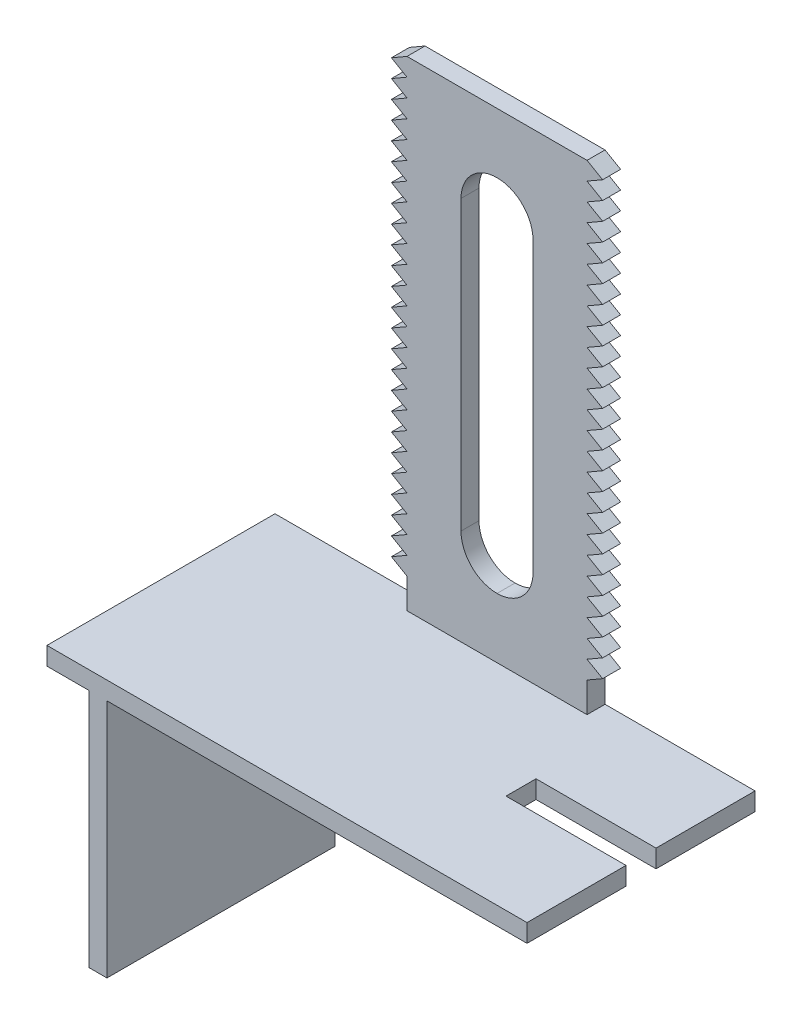
SolidWorks part; units mm, degrees
ref_plane "Front Plane" through (0, 0, 0) normal (0, 0, 1) x (1, 0, 0)
ref_plane "Top Plane" through (0, 0, 0) normal (0, 1, 0) x (1, 0, 0)
ref_plane "Right Plane" through (0, 0, 0) normal (1, 0, 0) x (0, 0, -1)
sketch "Sketch2" plane through (0, 0, 0) normal (0, 1, 0) x (1, 0, 0)
  line L1 (-15, 1.5) -> (15, 1.5)
  line L2 (-15, 1.5) -> (-15, -1.5)
  line L3 (-15, -1.5) -> (15, -1.5)
  line L4 (15, 1.5) -> (15, -1.5)
  line L5 (-15, 1.5) -> (15, -1.5) construction
  line L6 (-15, -1.5) -> (15, 1.5) construction
  point P0 (0, 0)
  dimension "D1" = 30
  dimension "D2" = 3
extrude "Boss-Extrude1" add sketch "Sketch2" along normal blind 80
sketch "Sketch3" plane through (0, 0, 1.5) normal (0, 0, 1) x (1, 0, 0)
  line L0 (15, 80) -> (17.5981, 78.5)
  line L1 (17.5981, 78.5) -> (15, 77)
  line L2 (15, 80) -> (15, 0) construction
  line L3 (15, 77) -> (15, 80)
  line L4 (15, 80) -> (15, 77)
  line L5 (15, 74) -> (15, 77)
  line L6 (17.5981, 75.5) -> (15, 74)
  line L7 (15, 77) -> (17.5981, 75.5)
  line L8 (15, 71) -> (15, 74)
  line L9 (17.5981, 72.5) -> (15, 71)
  line L10 (15, 74) -> (17.5981, 72.5)
  line L11 (15, 68) -> (15, 71)
  line L12 (17.5981, 69.5) -> (15, 68)
  line L13 (15, 71) -> (17.5981, 69.5)
  line L14 (15, 65) -> (15, 68)
  line L15 (17.5981, 66.5) -> (15, 65)
  line L16 (15, 68) -> (17.5981, 66.5)
  line L17 (15, 62) -> (15, 65)
  line L18 (17.5981, 63.5) -> (15, 62)
  line L19 (15, 65) -> (17.5981, 63.5)
  line L20 (15, 59) -> (15, 62)
  line L21 (17.5981, 60.5) -> (15, 59)
  line L22 (15, 62) -> (17.5981, 60.5)
  line L23 (15, 56) -> (15, 59)
  line L24 (17.5981, 57.5) -> (15, 56)
  line L25 (15, 59) -> (17.5981, 57.5)
  line L26 (15, 53) -> (15, 56)
  line L27 (17.5981, 54.5) -> (15, 53)
  line L28 (15, 56) -> (17.5981, 54.5)
  line L29 (15, 50) -> (15, 53)
  line L30 (17.5981, 51.5) -> (15, 50)
  line L31 (15, 53) -> (17.5981, 51.5)
  line L32 (15, 47) -> (15, 50)
  line L33 (17.5981, 48.5) -> (15, 47)
  line L34 (15, 50) -> (17.5981, 48.5)
  line L35 (15, 44) -> (15, 47)
  line L36 (17.5981, 45.5) -> (15, 44)
  line L37 (15, 47) -> (17.5981, 45.5)
  line L38 (15, 41) -> (15, 44)
  line L39 (17.5981, 42.5) -> (15, 41)
  line L40 (15, 44) -> (17.5981, 42.5)
  line L41 (15, 38) -> (15, 41)
  line L42 (17.5981, 39.5) -> (15, 38)
  line L43 (15, 41) -> (17.5981, 39.5)
  line L44 (15, 35) -> (15, 38)
  line L45 (17.5981, 36.5) -> (15, 35)
  line L46 (15, 38) -> (17.5981, 36.5)
  line L47 (15, 32) -> (15, 35)
  line L48 (17.5981, 33.5) -> (15, 32)
  line L49 (15, 35) -> (17.5981, 33.5)
  line L50 (15, 29) -> (15, 32)
  line L51 (17.5981, 30.5) -> (15, 29)
  line L52 (15, 32) -> (17.5981, 30.5)
  line L53 (15, 26) -> (15, 29)
  line L54 (17.5981, 27.5) -> (15, 26)
  line L55 (15, 29) -> (17.5981, 27.5)
  line L56 (15, 23) -> (15, 26)
  line L57 (17.5981, 24.5) -> (15, 23)
  line L58 (15, 26) -> (17.5981, 24.5)
  line L59 (15, 20) -> (15, 23)
  line L60 (17.5981, 21.5) -> (15, 20)
  line L61 (15, 23) -> (17.5981, 21.5)
  line L62 (15, 17) -> (15, 20)
  line L63 (17.5981, 18.5) -> (15, 17)
  line L64 (15, 20) -> (17.5981, 18.5)
  line L65 (15, 14) -> (15, 17)
  line L66 (17.5981, 15.5) -> (15, 14)
  line L67 (15, 17) -> (17.5981, 15.5)
  line L68 (15, 11) -> (15, 14)
  line L69 (17.5981, 12.5) -> (15, 11)
  line L70 (15, 14) -> (17.5981, 12.5)
  line L71 (15, 8) -> (15, 11)
  line L72 (17.5981, 9.5) -> (15, 8)
  line L73 (15, 11) -> (17.5981, 9.5)
  line L74 (15, 5) -> (15, 8)
  line L75 (17.5981, 6.5) -> (15, 5)
  line L76 (15, 8) -> (17.5981, 6.5)
  line L77 (-15, 80) -> (-15, 0) construction
  line L78 (-15, 80) -> (-17.5981, 78.5)
  line L79 (-17.5981, 78.5) -> (-15, 77)
  line L80 (-15, 77) -> (-15, 80)
  line L81 (-17.5981, 75.5) -> (-15, 74)
  line L82 (-15, 77) -> (-17.5981, 75.5)
  line L83 (-15, 74) -> (-15, 77)
  line L84 (-17.5981, 72.5) -> (-15, 71)
  line L85 (-15, 74) -> (-17.5981, 72.5)
  line L86 (-15, 71) -> (-15, 74)
  line L87 (-17.5981, 69.5) -> (-15, 68)
  line L88 (-15, 71) -> (-17.5981, 69.5)
  line L89 (-15, 68) -> (-15, 71)
  line L90 (-17.5981, 66.5) -> (-15, 65)
  line L91 (-15, 68) -> (-17.5981, 66.5)
  line L92 (-15, 65) -> (-15, 68)
  line L93 (-17.5981, 63.5) -> (-15, 62)
  line L94 (-15, 65) -> (-17.5981, 63.5)
  line L95 (-15, 62) -> (-15, 65)
  line L96 (-17.5981, 60.5) -> (-15, 59)
  line L97 (-15, 62) -> (-17.5981, 60.5)
  line L98 (-15, 59) -> (-15, 62)
  line L99 (-17.5981, 57.5) -> (-15, 56)
  line L100 (-15, 59) -> (-17.5981, 57.5)
  line L101 (-15, 56) -> (-15, 59)
  line L102 (-17.5981, 54.5) -> (-15, 53)
  line L103 (-15, 56) -> (-17.5981, 54.5)
  line L104 (-15, 53) -> (-15, 56)
  line L105 (-17.5981, 51.5) -> (-15, 50)
  line L106 (-15, 53) -> (-17.5981, 51.5)
  line L107 (-15, 50) -> (-15, 53)
  line L108 (-17.5981, 48.5) -> (-15, 47)
  line L109 (-15, 50) -> (-17.5981, 48.5)
  line L110 (-15, 47) -> (-15, 50)
  line L111 (-17.5981, 45.5) -> (-15, 44)
  line L112 (-15, 47) -> (-17.5981, 45.5)
  line L113 (-15, 44) -> (-15, 47)
  line L114 (-17.5981, 42.5) -> (-15, 41)
  line L115 (-15, 44) -> (-17.5981, 42.5)
  line L116 (-15, 41) -> (-15, 44)
  line L117 (-17.5981, 39.5) -> (-15, 38)
  line L118 (-15, 41) -> (-17.5981, 39.5)
  line L119 (-15, 38) -> (-15, 41)
  line L120 (-17.5981, 36.5) -> (-15, 35)
  line L121 (-15, 38) -> (-17.5981, 36.5)
  line L122 (-15, 35) -> (-15, 38)
  line L123 (-17.5981, 33.5) -> (-15, 32)
  line L124 (-15, 35) -> (-17.5981, 33.5)
  line L125 (-15, 32) -> (-15, 35)
  line L126 (-17.5981, 30.5) -> (-15, 29)
  line L127 (-15, 32) -> (-17.5981, 30.5)
  line L128 (-15, 29) -> (-15, 32)
  line L129 (-17.5981, 27.5) -> (-15, 26)
  line L130 (-15, 29) -> (-17.5981, 27.5)
  line L131 (-15, 26) -> (-15, 29)
  line L132 (-17.5981, 24.5) -> (-15, 23)
  line L133 (-15, 26) -> (-17.5981, 24.5)
  line L134 (-15, 23) -> (-15, 26)
  line L135 (-17.5981, 21.5) -> (-15, 20)
  line L136 (-15, 23) -> (-17.5981, 21.5)
  line L137 (-15, 20) -> (-15, 23)
  line L138 (-17.5981, 18.5) -> (-15, 17)
  line L139 (-15, 20) -> (-17.5981, 18.5)
  line L140 (-15, 17) -> (-15, 20)
  line L141 (-17.5981, 15.5) -> (-15, 14)
  line L142 (-15, 17) -> (-17.5981, 15.5)
  line L143 (-15, 14) -> (-15, 17)
  line L144 (-17.5981, 12.5) -> (-15, 11)
  line L145 (-15, 14) -> (-17.5981, 12.5)
  line L146 (-15, 11) -> (-15, 14)
  line L147 (-17.5981, 9.5) -> (-15, 8)
  line L148 (-15, 11) -> (-17.5981, 9.5)
  line L149 (-15, 8) -> (-15, 11)
  line L150 (-17.5981, 6.5) -> (-15, 5)
  line L151 (-15, 8) -> (-17.5981, 6.5)
  line L152 (-15, 5) -> (-15, 8)
  line M152 (15, 0) -> (15, 80)
  line M154 (-15, 80) -> (-15, 0)
  dimension "D1" = 3
  dimension "D2" = 3
  dimension "D3" = 3
  dimension "D5" = 30
  dimension "D6" = 2.5981
  dimension "D7" = 3
  dimension "D8" = 3
  dimension "D9" = 3
  dimension "D11" = 30
  dimension "D12" = 2.5981
  dimension "D4" = 25
  dimension "D10" = 25
extrude "Boss-Extrude2" add sketch "Sketch3" against normal blind 3 contours L78 L79 M154 | L82 L81 M154 | L85 L84 M154 | L88 L87 M154 | L91 L90 M154 | L94 L93 M154 | L97 L96 M154 | L100 L99 M154 | L103 L102 M154 | L106 L105 M154 | L109 L108 M154 | L1 L0 M152 | L7 L6 M152 | L10 L9 M152 | L13 L12 M152 | L16 L15 M152 | L19 L18 M152 | L22 L21 M152 | L25 L24 M152 | L28 L27 M152 | L31 L30 M152 | L34 L33 M152 | L112 L111 M154 | L115 L114 M154 | L118 L117 M154 | L121 L120 M154 | L124 L123 M154 | L127 L126 M154 | L130 L129 M154 | L133 L132 M154 | L136 L135 M154 | L139 L138 M154 | L142 L141 M154 | L145 L144 M154 | L148 L147 M154 | L151 L150 M154 | L37 L36 M152 | L43 L42 M152 | L46 L45 M152 | L49 L48 M152 | L61 L60 M152 | L64 L63 M152 | L67 L66 M152 | L70 L69 M152 | L73 L72 M152 | L40 L39 L38 | L52 L51 L50 | L55 L54 L53 | L58 L57 L56 | L76 L75 L74 region at (15.866, 9.5, 1.5) region at (15.866, 12.5, 1.5) region at (15.866, 15.5, 1.5) region at (15.866, 18.5, 1.5) region at (15.866, 21.5, 1.5) region at (15.866, 33.5, 1.5) region at (15.866, 36.5, 1.5) region at (15.866, 39.5, 1.5) region at (15.866, 45.5, 1.5) region at (15.866, 48.5, 1.5) region at (15.866, 51.5, 1.5) region at (15.866, 54.5, 1.5) region at (15.866, 57.5, 1.5) region at (15.866, 60.5, 1.5) region at (15.866, 63.5, 1.5) region at (15.866, 66.5, 1.5) region at (15.866, 69.5, 1.5) region at (15.866, 72.5, 1.5) region at (15.866, 75.5, 1.5) region at (15.866, 78.5, 1.5) region at (-15.866, 78.5, 1.5) region at (-15.866, 6.5, 1.5) region at (-15.866, 9.5, 1.5) region at (-15.866, 12.5, 1.5) region at (-15.866, 15.5, 1.5) region at (-15.866, 18.5, 1.5) region at (-15.866, 21.5, 1.5) region at (-15.866, 24.5, 1.5) region at (-15.866, 27.5, 1.5) region at (-15.866, 30.5, 1.5) region at (-15.866, 33.5, 1.5) region at (-15.866, 36.5, 1.5) region at (-15.866, 39.5, 1.5) region at (-15.866, 42.5, 1.5) region at (-15.866, 45.5, 1.5) region at (-15.866, 48.5, 1.5) region at (-15.866, 51.5, 1.5) region at (-15.866, 54.5, 1.5) region at (-15.866, 57.5, 1.5) region at (-15.866, 60.5, 1.5) region at (-15.866, 63.5, 1.5) region at (-15.866, 66.5, 1.5) region at (-15.866, 69.5, 1.5) region at (-15.866, 72.5, 1.5) region at (-15.866, 75.5, 1.5)
sketch "Sketch4" plane through (0, 0, 1.5) normal (0, 0, 1) x (1, 0, 0)
  line L0 (-9, 0) -> (-9, -3)
  line L1 (-15, 0) -> (15, 0)
  line L2 (-15, 0) -> (-15, -6)
  line L3 (-15, -6) -> (15, -6)
  line L4 (15, 0) -> (15, -6)
  line L5 (-15, 0) -> (-12, 0)
  line L6 (-15, 0) -> (-15, -3)
  line L7 (-15, -3) -> (-12, -3)
  line L8 (-12, 0) -> (-12, -3)
  line L9 (-12, -3) -> (-9, -3)
  line L10 (-6, 0) -> (-6, -3)
  line L11 (-9, -3) -> (-6, -3)
  line L12 (-3, 0) -> (-3, -3)
  line L13 (-6, -3) -> (-3, -3)
  line L14 (0, 0) -> (0, -3)
  line L15 (-3, -3) -> (0, -3)
  line L16 (3, 0) -> (3, -3)
  line L17 (0, -3) -> (3, -3)
  line L18 (6, 0) -> (6, -3)
  line L19 (3, -3) -> (6, -3)
  line L20 (9, 0) -> (9, -3)
  line L21 (6, -3) -> (9, -3)
  line L22 (12, 0) -> (12, -3)
  line L23 (9, -3) -> (12, -3)
  line L24 (15, 0) -> (15, -3)
  line L25 (12, -3) -> (15, -3)
  dimension "D1" = 6
  dimension "D2" = 30
  dimension "D3" = 3
  dimension "D4" = 3
  dimension "D6" = 6
  dimension "D7" = 3
  dimension "D5" = 10
extrude "Boss-Extrude3" add sketch "Sketch4" against normal blind 3 contours L25 L23 L21 L19 L17 L15 L13 L11 L9 L7 L2 L3 L4 | L8 L1 L2 L7 | L0 L11 L10 L1 | L12 L15 L14 L1 | L14 L17 L16 L1 | L18 L21 L20 L1 | L22 L25 L4 L1 region at (-7.5, -1.5, 1.5) region at (0, -4.5, 1.5) region at (-13.5, -1.5, 1.5) region at (-1.5, -1.5, 1.5) region at (1.5, -1.5, 1.5) region at (7.5, -1.5, 1.5) region at (13.5, -1.5, 1.5)
sketch "Sketch5" plane through (0, 0, -1.5) normal (0, 0, -1) x (-1, 0, 0)
  line L0 (-15, 5) -> (-15, -6) construction
  line L1 (-6, 70) -> (6, 70)
  line L2 (-6, 70) -> (-6, 10)
  line L3 (-6, 10) -> (6, 10)
  line L4 (6, 70) -> (6, 10)
  line L5 (15, -6) -> (-15, -6) construction
  dimension "D1" = 12
  dimension "D2" = 60
  dimension "D3" = 9
  dimension "D4" = 16
extrude "Cut-Extrude1" cut sketch "Sketch5" against normal blind 3
fillet "Fillet1" radius 6 4 edges at (-6, 10, 0) (6, 10, 0) (6, 70, 0) (-6, 70, 0)
sketch "Sketch7" plane through (0, 0, 1.5) normal (0, 0, 1) x (1, 0, 0)
  line L0 (-15, 5) -> (-15, -6) construction
  line L1 (-15, 0) -> (15, 0)
  line L2 (-15, 0) -> (-15, -3)
  line L3 (-15, -3) -> (15, -3)
  line L4 (15, 0) -> (15, -3)
  line L5 (15, 5) -> (15, -6) construction
  line L6 (-15, -6) -> (15, -6) construction
  line L8 (-15, 0) -> (-12, 0)
  line L9 (-15, 0) -> (-15, -3)
  line L10 (-15, -3) -> (-12, -3)
  line L11 (-12, 0) -> (-12, -3)
  line L12 (-12, -3) -> (-9, -3)
  line L13 (-12, -3) -> (-12, 0)
  line L14 (-12, 0) -> (-9, 0)
  line L15 (-9, -3) -> (-9, 0)
  line L16 (-9, 0) -> (-6, 0)
  line L17 (-9, 0) -> (-9, -3)
  line L18 (-9, -3) -> (-6, -3)
  line L19 (-6, 0) -> (-6, -3)
  line L20 (-6, -3) -> (-3, -3)
  line L21 (-6, -3) -> (-6, 0)
  line L22 (-6, 0) -> (-3, 0)
  line L23 (-3, -3) -> (-3, 0)
  line L24 (-3, 0) -> (3, 0)
  line L25 (-3, 0) -> (-3, -3)
  line L26 (-3, -3) -> (3, -3)
  line L27 (3, 0) -> (3, -3)
  line L28 (3, -3) -> (6, -3)
  line L29 (3, -3) -> (3, 0)
  line L30 (3, 0) -> (6, 0)
  line L31 (6, -3) -> (6, 0)
  line L32 (6, 0) -> (9, 0)
  line L33 (6, 0) -> (6, -3)
  line L34 (6, -3) -> (9, -3)
  line L35 (9, 0) -> (9, -3)
  line L36 (9, -3) -> (12, -3)
  line L37 (9, -3) -> (9, 0)
  line L38 (9, 0) -> (12, 0)
  line L39 (12, -3) -> (12, 0)
  line L40 (12, 0) -> (15, 0)
  line L41 (12, 0) -> (12, -3)
  line L42 (12, -3) -> (15, -3)
  line L43 (15, 0) -> (15, -3)
  dimension "D1" = 3
  dimension "D2" = 3
extrude "Boss-Extrude8" add sketch "Sketch7" along normal blind 10 contours L11 L1 L2 L3 | L19 L1 L15 L3 | L27 L1 L23 L3 | L35 L1 L31 L3 | L39 L3 L4 L1 region at (-13.5, -1.5, 1.5) region at (-7.5, -1.5, 1.5) region at (0, -1.5, 1.5) region at (7.5, -1.5, 1.5) region at (13.5, -1.5, 1.5)
sketch "Sketch8" plane through (-9, 0, 0) normal (-1, 0, 0) x (0, 0, 1)
  line L1 (-1.5, 0) -> (11.5, 0)
  line L2 (-1.5, 0) -> (-1.5, -3)
  line L3 (-1.5, -3) -> (11.5, -3)
  line L4 (11.5, 0) -> (11.5, -3)
extrude "Boss-Extrude9" add sketch "Sketch8" along normal blind 3
sketch "Sketch9" plane through (-3, 0, 0) normal (-1, 0, 0) x (0, 0, 1)
  line L1 (-1.5, 0) -> (11.5, 0)
  line L2 (-1.5, 0) -> (-1.5, -3)
  line L3 (-1.5, -3) -> (11.5, -3)
  line L4 (11.5, 0) -> (11.5, -3)
extrude "Boss-Extrude10" add sketch "Sketch9" along normal blind 3
sketch "Sketch10" plane through (6, 0, 0) normal (-1, 0, 0) x (0, 0, 1)
  line L1 (-1.5, 0) -> (11.5, 0)
  line L2 (-1.5, 0) -> (-1.5, -3)
  line L3 (-1.5, -3) -> (11.5, -3)
  line L4 (11.5, 0) -> (11.5, -3)
extrude "Boss-Extrude11" add sketch "Sketch10" along normal blind 3
sketch "Sketch11" plane through (12, 0, 0) normal (-1, 0, 0) x (0, 0, 1)
  line L1 (-1.5, 0) -> (11.5, 0)
  line L2 (-1.5, 0) -> (-1.5, -3)
  line L3 (-1.5, -3) -> (11.5, -3)
  line L4 (11.5, 0) -> (11.5, -3)
extrude "Boss-Extrude12" add sketch "Sketch11" along normal blind 3
sketch "Sketch12" plane through (-15, 0, 0) normal (-1, 0, 0) x (0, 0, 1)
  line L0 (-1.5, 5) -> (-1.5, -6) construction
  line L1 (11.5, 0) -> (-1.5, 0)
  line L2 (11.5, 0) -> (11.5, -3)
  line L3 (11.5, -3) -> (-1.5, -3)
  line L4 (-1.5, 0) -> (-1.5, -3)
  dimension "D1" = 3
extrude "Boss-Extrude13" add sketch "Sketch12" along normal blind 25
sketch "Sketch13" plane through (15, 0, 0) normal (1, 0, 0) x (0, 0, -1)
  line L0 (1.5, 5) -> (1.5, -6) construction
  line L1 (-11.5, 0) -> (1.5, 0)
  line L2 (-11.5, 0) -> (-11.5, -3)
  line L3 (-11.5, -3) -> (1.5, -3)
  line L4 (1.5, 0) -> (1.5, -3)
  dimension "D1" = 3
extrude "Boss-Extrude14" add sketch "Sketch13" along normal blind 25
sketch "Sketch14" plane through (0, 0, 11.5) normal (0, 0, 1) x (1, 0, 0)
  line L1 (-40, 0) -> (40, 0)
  line L2 (-40, 0) -> (-40, -3)
  line L3 (-40, -3) -> (40, -3)
  line L4 (40, 0) -> (40, -3)
extrude "Boss-Extrude15" add sketch "Sketch14" along normal blind 25
sketch "Sketch15" plane through (0, -3, 0) normal (0, -1, 0) x (1, 0, 0)
  line L0 (-40, 36.5) -> (40, 36.5) construction
  line L1 (-33, 36.5) -> (-30, 36.5)
  line L2 (-33, 36.5) -> (-33, -1.5)
  line L3 (-33, -1.5) -> (-30, -1.5)
  line L4 (-30, 36.5) -> (-30, -1.5)
  line L5 (-40, -1.5) -> (-15, -1.5) construction
  line L6 (-15, -1.5) -> (-15, 1.5) construction
  dimension "D1" = 3
  dimension "D2" = 15
extrude "Boss-Extrude16" add sketch "Sketch15" along normal blind 40
sketch "Sketch16" plane through (0, -3, 0) normal (0, -1, 0) x (1, 0, 0)
  line L0 (40, 36.5) -> (40, -1.5) construction
  line L1 (40, 20) -> (20, 20)
  line L2 (40, 20) -> (40, 15)
  line L3 (40, 15) -> (20, 15)
  line L4 (20, 20) -> (20, 15)
  line L7 (40, -1.5) -> (15, -1.5) construction
  dimension "D1" = 5
  dimension "D2" = 20
  dimension "D3" = 16.5
extrude "Cut-Extrude2" cut sketch "Sketch16" against normal blind 3
